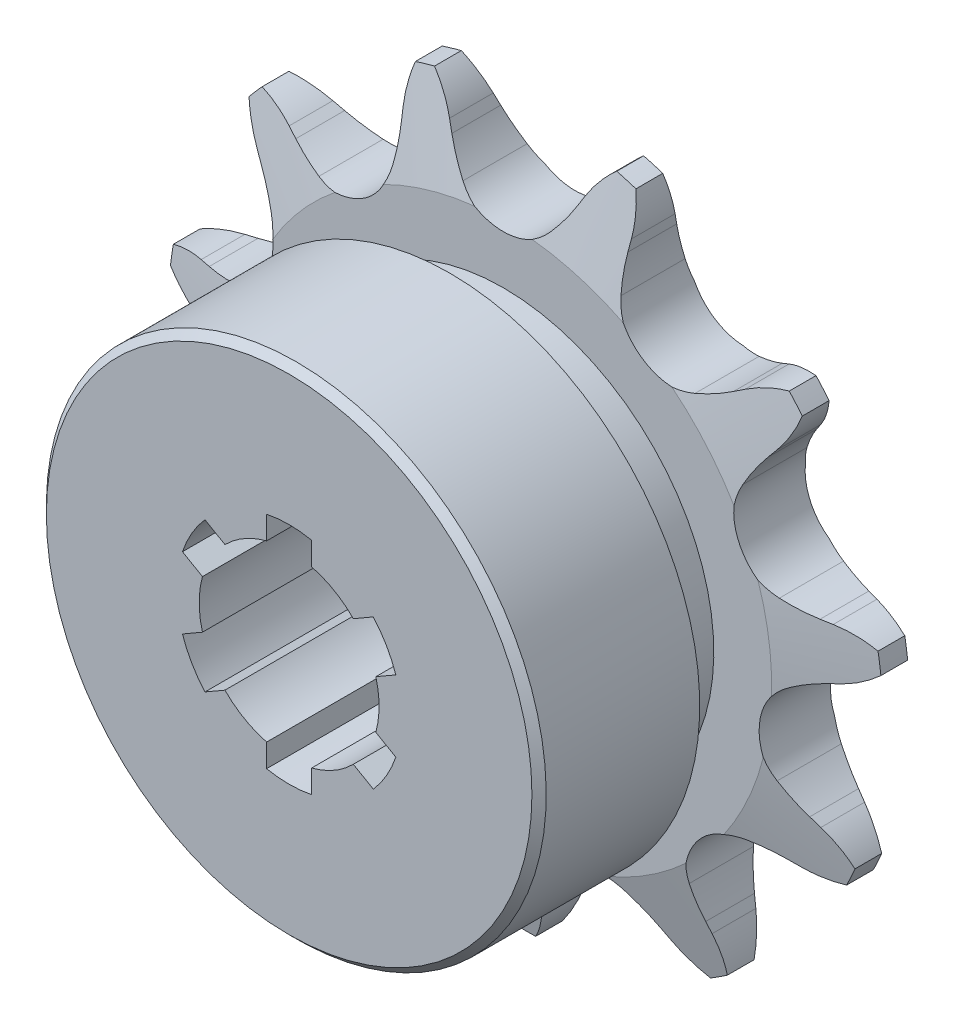
SolidWorks part; units mm, degrees
ref_plane "Front Plane" through (0, 0, 0) normal (0, 0, 1) x (1, 0, 0)
ref_plane "Top Plane" through (0, 0, 0) normal (0, 1, 0) x (1, 0, 0)
ref_plane "Right Plane" through (0, 0, 0) normal (1, 0, 0) x (0, 0, -1)
sketch "Sketch0" plane through (0, 0, 0) normal (0, 0, 1) x (1, 0, 0)
  line L0 (7.9375, -27.0326) -> (0, 0) construction
  line L1 (0, 0) -> (21.2924, -18.45) construction
  line L2 (0, 0) -> (-7.9375, -27.0326) construction
  line L3 (7.9375, -27.0326) -> (21.2924, -18.45) construction
  line L4 (7.9375, -27.0326) -> (-7.9375, -27.0326) construction
  line L5 (13.7041, -25.3103) -> (13.0504, -24.6313)
  line L6 (7.9375, -27.0326) -> (0, -29.3633) construction
  line L7 (2.1552, -28.7014) -> (2.338, -27.7767)
  line L8 (0, -27.0326) -> (0, -31.7951) construction
  line L9 (10.7525, -22.7279) -> (3.4891, -33.8353) construction
  line L10 (0, 0) -> (0, -27.0326) construction
  line L11 (13.0504, -24.6313) -> (3.4891, -33.8353) construction
  line L12 (0, -31.7951) -> (0, -32.9086) construction
  line L13 (19.9035, -19.3426) -> (13.7041, -25.3103) construction
  circle A0 centre (0, 0) radius 31.7951 construction
  circle A1 centre (0, 0) radius 28.1739 construction
  arc A2 (-8.2356, -35.414) -> (26.0745, -25.3397) centre (0, 0) ccw
  circle A3 centre (0, 0) radius 32.9086 construction
  circle A4 centre (7.9375, -27.0326) radius 5.08 construction
  arc A7 (10.7525, -22.7279) -> (3.242, -24.9331) centre (7.9375, -27.0326) ccw
  circle A8 centre (7.9375, -27.0326) radius 5.1435 construction
  arc A9 (13.7041, -25.3103) -> (26.0745, -25.3397) centre (19.9035, -19.3426) ccw
  arc A10 (13.0504, -24.6313) -> (10.7525, -22.7279) centre (3.4891, -33.8353) ccw
  arc A11 (2.1552, -28.7014) -> (-8.2356, -35.414) centre (-6.2865, -27.0326) cw
  arc A12 (2.338, -27.7767) -> (3.242, -24.9331) centre (15.3575, -30.3504) cw
  dimension "D1" = 5.1435
  dimension "R" = 5.1435
sketch "Sketch1" plane through (0, 0, 0) normal (1, 0, 0) x (0, 0, -1)
  line L0 (3.175, 0) -> (-3.175, 0)
  line L1 (-3.175, 0) -> (-3.175, 23.8576)
  line L2 (-3.175, 23.8576) -> (-1.1906, 31.7951)
  line L3 (-1.1906, 31.7951) -> (1.1906, 31.7951)
  line L4 (1.1906, 31.7951) -> (3.175, 23.8576)
  line L5 (3.175, 23.8576) -> (3.175, 0)
  line L7 (0, 31.7951) -> (0, 0) construction
  line L8 (-3.175, 23.8576) -> (3.175, 23.8576) construction
  line L9 (0, 31.7951) -> (0, -31.7951) construction
  line L10 (-3.175, 23.8576) -> (-3.175, 31.7951) construction
  line L11 (-3.175, 31.7951) -> (-1.1906, 31.7951) construction
  line L12 (1.1906, 31.7951) -> (3.175, 31.7951) construction
  line L13 (3.175, 31.7951) -> (3.175, 23.8576) construction
  line L14 (0, 0) -> (-6.4008, 0) construction
  line L22 (3.175, 0) -> (-22.225, 0) construction
  line L24 (-3.175, 0) -> (-3.175, 18.7141) construction
revolve "Revolve1" add sketch "Sketch1" angle 360 mid plane about L0
extrude "Cut-Extrude1" cut sketch "Sketch0" against normal through all and the other way through all
pattern_circular "CirPattern1" count 11 over 360 about axis through (0, 0, -3.175) along (0, 0, -1) of "Cut-Extrude1"
sketch "Sketch2" plane through (0, 0, 0) normal (0, 0, 1) x (1, 0, 0)
  circle A0 centre (0, 0) radius 7.9375 construction
  circle A1 centre (0, 0) radius 22.225
  circle A2 centre (0, 0) radius 31.75 construction
  dimension "Bore" = 15.875
  dimension "Hub Dia." = 44.45
  dimension "OD" = 63.5
extrude "Boss-Extrude1" add sketch "Sketch2" along normal up to vertex (22.225 mm away) from surface up to point (0, 0, 22.225) starting at face at (0, 0, 3.175)
sketch "Sketch3" plane through (0, 0, 0) normal (0, 0, 1) x (1, 0, 0)
  circle A0 centre (0, 0) radius 7.9375 construction
  circle A1 centre (0, 0) radius 7.9375
extrude "Cut-Extrude2" cut sketch "Sketch3" along normal through all and the other way through all
sketch "Sketch4" plane through (0, 0, 0) normal (1, 0, 0) x (0, 0, -1)
  line L0 (-22.225, 22.225) -> (-22.225, 21.59)
  line L1 (-3.175, 31.7951) -> (-7.9375, 31.7951)
  line L2 (-3.175, 31.7951) -> (-3.175, 18.7141)
  line L3 (-3.175, 18.7141) -> (-7.9375, 18.7141)
  line L4 (-7.9375, 31.7951) -> (-7.9375, 18.7141)
  line L9 (-22.225, 21.59) -> (-21.59, 22.225)
  line L10 (-21.59, 22.225) -> (-22.225, 22.225)
  dimension "C" = 0.635
  dimension "D3" = 4.7625
revolve "Cut-Revolve1" cut sketch "Sketch4" angle 360 mid plane about L22
ref_plane "Plane1" through (0, 0, 0) normal (0, 0, -1) x (-1, 0, 0)
ref_axis "Axis1" through (0, 0, 36.6519) along (0, 0, -1)
sketch "Sketch5" plane through (0, 0, -3.175) normal (0, 0, -1) x (-1, 0, 0)
  line L0 (7.6603, -6.7321) -> (9.6603, -3.2679)
  line L1 (2, -10) -> (-2, -10)
  line L2 (2, -10) -> (2, 10)
  line L3 (2, 10) -> (-2, 10)
  line L4 (-2, -10) -> (-2, 10)
  line L5 (2, -10) -> (-2, 10) construction
  line L6 (2, 10) -> (-2, -10) construction
  line L7 (-7.6603, 6.7321) -> (9.6603, -3.2679)
  line L8 (-9.6603, 3.2679) -> (7.6603, -6.7321)
  line L9 (-9.6603, 3.2679) -> (-7.6603, 6.7321)
  line L10 (-9.6603, -3.2679) -> (-7.6603, -6.7321)
  line L11 (9.6603, 3.2679) -> (-7.6603, -6.7321)
  line L12 (7.6603, 6.7321) -> (-9.6603, -3.2679)
  line L13 (7.6603, 6.7321) -> (9.6603, 3.2679)
  circle A0 centre (0, 0) radius 8
  circle A1 centre (0, 0) radius 10
  point P18 (0, 0)
  dimension "D1" = 16
  dimension "D2" = 20
  dimension "D3" = 4
  dimension "D4" = 3
extrude "Cut-Extrude3" cut sketch "Sketch5" against normal through all contours L2 A1 L4 A0 | L11 A1 L12 A0 | L8 A1 L7 A0 | L4 A1 L2 A0 | L12 A1 L11 A0 | L7 A1 L8 A0 | A0 region at (-7.7283, -4.4619, -3.175) region at (0, -8.9239, -3.175) region at (-7.7283, 4.4619, -3.175) region at (7.7283, -4.4619, -3.175) region at (0, 8.9239, -3.175) region at (7.7283, 4.4619, -3.175)
equation "\"360/N@Sketch0\" = 360/\"Teeth@CirPattern1\""
equation "\"Ds@Sketch0\" = 1.005 * \"Dr@Sketch0\" + 0.003"
equation "\"R@Sketch0\" = 1/2 * \"Ds@Sketch0\""
equation "\"A@Sketch0\" = 35 +  ( 60 / \"Teeth@CirPattern1\" ) "
equation "\"B@Sketch0\" = 18 -  ( 56 / \"Teeth@CirPattern1\" )"
equation "\"ac@Sketch0\" = 0.8 * \"Dr@Sketch0\""
equation "\"ab@Sketch0\" = 1.4 * \"Dr@Sketch0\""
equation "\"J@Sketch0\" = 0.3 * \"Pitch@Sketch0\""
equation "\"h@Sketch1\" = \"Pitch@Sketch0\" / 2"
equation "\"g@Sketch1\" = \"h@Sketch1\" / 4"
equation "\"MHD@Sketch1\" = \"Pitch@Sketch0\" * ( cotan ( 180 / \"Teeth@CirPattern1\" ) - 1 ) - 0.030"
equation "\"D3@Sketch4\" = \"t@Sketch1\" * 3 / 4"
